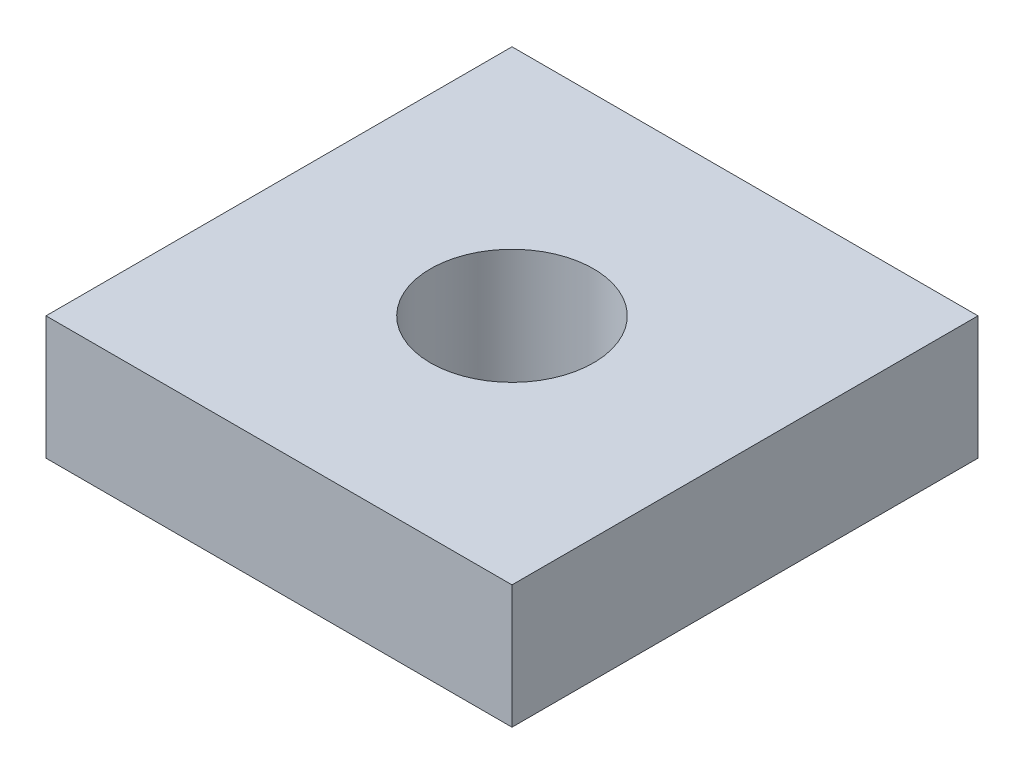
SolidWorks part; units mm, degrees
ref_plane "Front Plane" through (0, 0, 0) normal (0, 0, 1) x (1, 0, 0)
ref_plane "Top Plane" through (0, 0, 0) normal (0, 1, 0) x (1, 0, 0)
ref_plane "Right Plane" through (0, 0, 0) normal (1, 0, 0) x (0, 0, -1)
sketch "Sketch2" plane through (0, 0, 0) normal (0, 1, 0) x (1, 0, 0)
  line L0 (-12, 6) -> (0, 6) construction
  line L1 (0, 0) -> (-12, 0)
  line L2 (0, 0) -> (0, 12)
  line L3 (0, 12) -> (-12, 12)
  line L4 (-12, 0) -> (-12, 12)
  line L5 (-6, 0) -> (-6, 12) construction
  circle A1 centre (-6, 6) radius 2.1
  dimension "D1" = 4.2
extrude "Boss-Extrude1" add sketch "Sketch2" along normal blind 3.175
